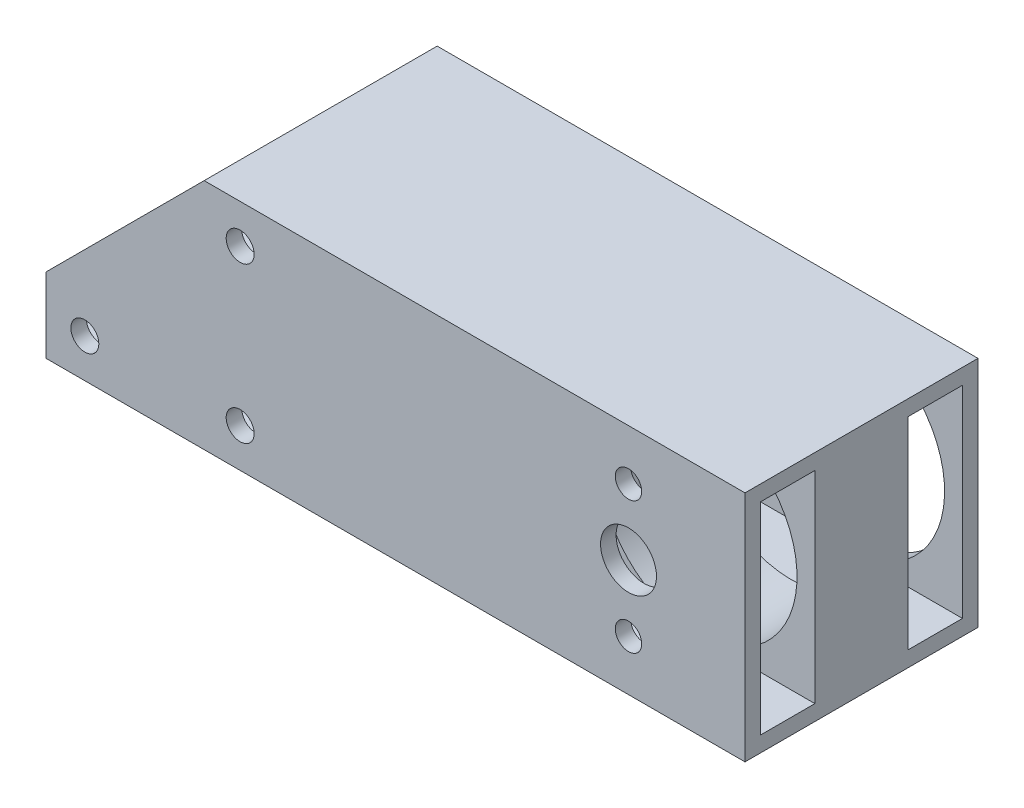
SolidWorks part; units mm, degrees
material "PLA 15%"
ref_plane "Front Plane" through (0, 0, 0) normal (0, 0, 1) x (1, 0, 0)
ref_plane "Top Plane" through (0, 0, 0) normal (0, 1, 0) x (1, 0, 0)
ref_plane "Right Plane" through (0, 0, 0) normal (1, 0, 0) x (0, 0, -1)
sketch "Sketch1" plane through (0, 0, 0) normal (1, 0, 0) x (0, 0, -1)
  line L1 (-15, -15) -> (15, -15)
  line L2 (-15, -15) -> (-15, 15)
  line L3 (-15, 15) -> (15, 15)
  line L4 (15, -15) -> (15, 15)
  line L5 (-15, -15) -> (15, 15) construction
  line L6 (-15, 15) -> (15, -15) construction
  line L11 (-5.1844, 5.1844) -> (5.1844, -5.1844) construction
  line L12 (-5.1844, -5.1844) -> (5.1844, 5.1844) construction
  line L13 (-13, 13) -> (-6, 13)
  line L14 (-13, 13) -> (-13, -13)
  line L15 (-13, -13) -> (-6, -13)
  line L16 (-6, 13) -> (-6, -13)
  line L17 (13, 13) -> (6, 13)
  line L18 (13, 13) -> (13, -13)
  line L19 (13, -13) -> (6, -13)
  line L20 (6, 13) -> (6, -13)
  point P0 (0, 0)
  point P7 (0, 0)
  dimension "D1" = 30
  dimension "D2" = 30
  dimension "D3" = 2
  dimension "D4" = 7
  dimension "D5" = 2
  dimension "D6" = 7
  dimension "D7" = 2
  dimension "D8" = 2
extrude "Boss-Extrude3" add sketch "Sketch1" along normal blind 90
sketch "Sketch6" plane through (0, 0, -15) normal (0, 0, -1) x (-1, 0, 0)
  line L0 (-90, -15) -> (-90, 15) construction
  circle A0 centre (-75, 0) radius 12.7
  dimension "D2" = 25.4
  dimension "D1" = 15
extrude "Cut-Extrude5" cut sketch "Sketch6" against normal blind 23
sketch "Sketch8" plane through (0, 0, 15) normal (0, 0, 1) x (1, 0, 0)
  line L0 (90, 15) -> (90, -15) construction
  line L1 (75, 0) -> (90, 0) construction
  circle A0 centre (75, 0) radius 3.6
  circle A1 centre (75, 8.5) radius 1.7
  circle A2 centre (75, -8.5) radius 1.7
  dimension "D2" = 7.2
  dimension "D5" = 3.4
  dimension "D1" = 15
  dimension "D3" = 17
extrude "Cut-Extrude6" cut sketch "Sketch8" against normal blind 17
sketch "Sketch9" plane through (0, 0, 0) normal (-1, 0, 0) x (0, 0, 1)
  line L0 (-6, 13) -> (6, 13)
  line L1 (-6, -13) -> (6, -13)
  line L2 (-6, 13) -> (-6, -13)
  line L3 (6, 13) -> (6, -13)
extrude "Cut-Extrude7" cut sketch "Sketch9" against normal blind 59
sketch "Sketch11" plane through (0, 0, 15) normal (0, 0, 1) x (1, 0, 0)
  line L13 (25, 10) -> (25, -10) construction
  line L16 (5, -10) -> (90, -10)
  line L17 (5, 10) -> (5, -10)
  line L18 (90, 10) -> (5, 10)
  line L19 (5, -10) -> (25, -10) construction
  line L20 (5, 10) -> (5, -10) construction
  line L21 (25, 10) -> (5, 10) construction
  point P12 (5, -10)
  point P14 (25, -10)
  point P15 (5, 10)
  point P16 (25, 10)
  dimension "D1" = 5
hole_wizard "M3 Clearance Hole1" positions "Sketch11" profile "Sketch12" hole size "M3" standard "ANSI Metric" end condition through all
sketch "Sketch12" plane through (25, 10, 15) normal (1, 0, 0) x (0, -1, 0)
  line L0 (0, 0) -> (0, 30)
  line L1 (0, 30) -> (1.8, 30)
  line L2 (1.8, 30) -> (1.8, 0)
  line L5 (1.8, 0) -> (0, 0)
  line L11 (0, -6.35) -> (0, 107.95) construction
  dimension "Thru Hole Dia." = 3.6
  dimension "Thru Hole Depth" = 30
sketch "Sketch13" plane through (0, 0, 0) normal (0, 0, 1) x (1, 0, 0)
  line L0 (0, -5.3647) -> (20.3647, 15)
  line L1 (0, 15) -> (0, -15) construction
  line L2 (90, 15) -> (0, 15) construction
  line L3 (20.3647, 15) -> (0, 15)
  line L4 (0, 15) -> (0, -5.3647)
  dimension "D1" = 45
  dimension "D2" = 28.8
extrude "Cut-Extrude8" cut sketch "Sketch13" against normal blind 26 and the other way blind 28
